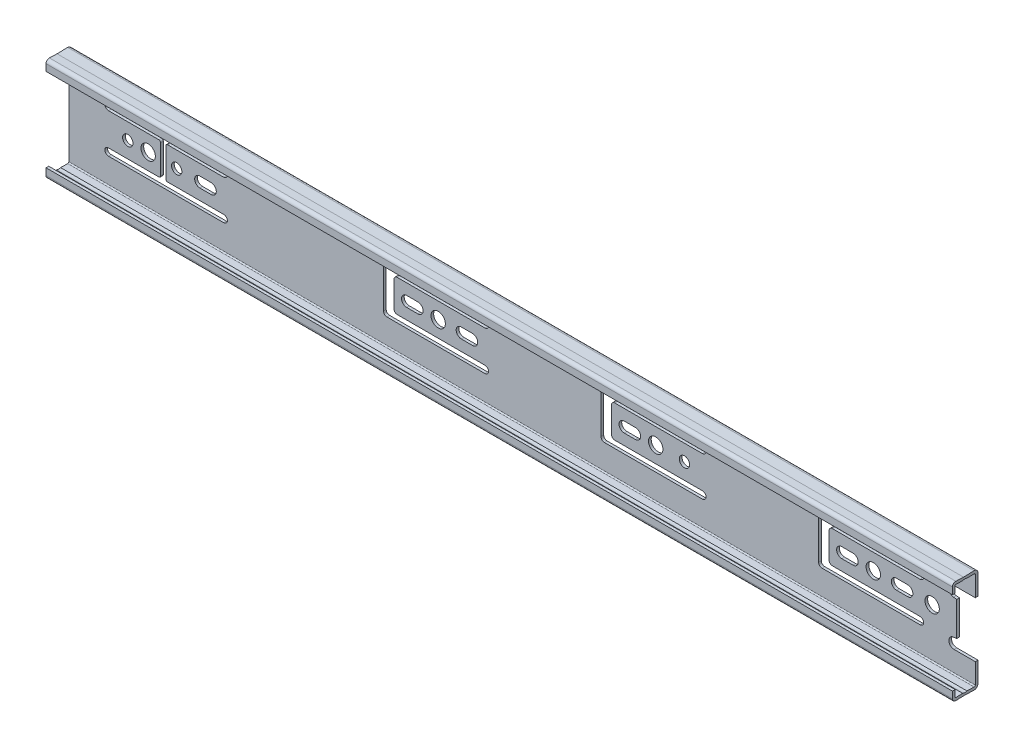
SolidWorks part; units mm, degrees
ref_plane "Front" through (0, 0, 0) normal (0, 0, 1) x (1, 0, 0)
ref_plane "Top" through (0, 0, 0) normal (0, 1, 0) x (1, 0, 0)
ref_plane "Right" through (0, 0, 0) normal (1, 0, 0) x (0, 0, -1)
sketch "Sketch1" plane through (0, 0, 0) normal (1, 0, 0) x (0, 0, -1)
  line L1 (5.6388, 0) -> (-5.6388, 0) construction
  line L4 (-4.1393, 22.8203) -> (-0.7433, 22.6989)
  line L5 (-1.1312, 21.5182) -> (-4.1819, 21.6273)
  line L6 (-4.445, 18.415) -> (-5.6388, 18.415)
  line L7 (-4.445, 21.3734) -> (-4.445, 18.415)
  line L8 (-5.6388, 18.415) -> (-5.6388, 21.3734)
  line L9 (3.9237, 21.6269) -> (0.7619, 21.5441)
  line L10 (5.6388, 0) -> (5.6388, 21.1191)
  line L11 (4.445, 21.1191) -> (4.445, 0)
  line L12 (5.6388, 0) -> (4.445, 0)
  line L13 (-0.7433, 22.6989) -> (3.8925, 22.8203)
  arc A0 (-4.445, 21.3734) -> (-4.1819, 21.6273) centre (-4.191, 21.3734) cw
  arc A1 (-5.6388, 21.3734) -> (-4.1393, 22.8203) centre (-4.191, 21.3734) cw
  arc A3 (3.9237, 21.6269) -> (4.445, 21.1191) centre (3.937, 21.1191) cw
  arc A4 (3.8925, 22.8203) -> (5.6388, 21.1191) centre (3.937, 21.1191) cw
  arc A5 (-1.1312, 21.5182) -> (0.7619, 21.5441) centre (-0.1524, 19.1744) cw
  dimension "D2" = 19.1744
  dimension "D7" = 0.254
  dimension "D8" = 0.508
  dimension "D6" = 2.54
  dimension "D9" = 1.1938
  dimension "D10" = 88.5
  dimension "D1" = 11.2776
  dimension "D3" = 5.7912
  dimension "D4" = 36.83
  dimension "D5" = 1.1938
  dimension "D11" = 87.953
  dimension "D12" = 45.6406
extrude "Extrude1" add sketch "Sketch1" along normal mid plane 400.05
ref_plane "Travel / 2" through (-403.225, 0, 0) normal (-1, 0, 0) x (0, 0, 1)
sketch "Sketch2" plane through (-403.225, 0, 0) normal (-1, 0, 0) x (0, 0, 1)
  line L0 (0.0254, 6.1159) -> (0.0254, 0)
  line L2 (-5.6388, 0) -> (5.6388, 0) construction
  line L3 (5.6388, 21.3734) -> (5.6388, 18.415) construction
  line L7 (-4.445, 21.1191) -> (-4.445, 0) construction
  line L8 (-5.6388, 0) -> (-5.6388, 21.1191) construction
  line L13 (-3.5306, 16.3766) -> (-3.5306, 9.5217)
  line L46 (-2.3867, 7.7262) -> (-0.4146, 6.8065)
  arc A0 (0.0254, 6.1159) -> (-0.4146, 6.8065) centre (-0.7366, 6.1159) ccw
  arc A1 (-1.5056, 17.2916) -> (1.2415, 16.9143) centre (0.1524, 19.1744) ccw
  arc A4 (1.1312, 21.5182) -> (-0.7619, 21.5441) centre (0.1524, 19.1744) ccw construction
  arc A19 (-3.5306, 9.5217) -> (-2.3867, 7.7262) centre (-1.5494, 9.5217) ccw
  arc A25 (-1.5056, 17.2916) -> (-3.5306, 16.3766) centre (-2.3114, 16.3766) ccw
  arc A51 (5.7404, 15.6277) -> (1.2415, 16.9143) centre (2.7686, 13.7451) ccw
  dimension "D2" = 8.4074
  dimension "D3" = 27.4903
  dimension "D6" = 1.9812
  dimension "D8" = 12.2319
  dimension "D10" = 2.5088
  dimension "D11" = 1.2192
  dimension "D4" = 0.762
  dimension "D5" = 4.4704
  dimension "D7" = 115
  dimension "D9" = 19.0435
  dimension "D13" = 11.3792
extrude "Middle Member" add sketch "Sketch2" against normal blind 400.05 separate body thin thin type one direction reverse wall 1.2192
ref_plane "Travel" through (-606.425, 0, 0) normal (-1, 0, 0) x (0, 0, 1)
sketch "Sketch3" plane through (-606.425, 0, 0) normal (-1, 0, 0) x (0, 0, 1)
  line L0 (1.2446, 0) -> (0.0254, 0) construction
  line L1 (-5.6388, 0) -> (-5.6388, 21.1191) construction
  line L56 (7.0612, 0) -> (7.0612, 10.6235)
  line L93 (5.5372, 12.1475) -> (5.1643, 12.1475)
  arc A0 (1.2082, 11.9072) -> (4.2365, 11.8325) centre (2.7686, 13.7451) ccw
  arc A29 (7.0612, 10.6235) -> (5.5372, 12.1475) centre (5.5372, 10.6235) ccw
  arc A53 (5.1643, 12.1475) -> (4.2365, 11.8325) centre (5.1643, 10.6235) ccw
  dimension "D1" = 1.524
  dimension "D4" = 1.524
  dimension "D5" = 2.411
  dimension "D2" = 12.7
  dimension "D3" = 12.1475
  dimension "D6" = 5.853
extrude "Drawer Member" add sketch "Sketch3" against normal blind 400.05 thin thin type one direction wall 1.397
sketch "Sketch6" plane through (0, 0, 7.0612) normal (0, 0, 1) x (1, 0, 0)
  line L1 (-606.425, 0) -> (-604.52, 0)
  line L2 (-606.425, 0) -> (-606.425, 12.1475)
  line L3 (-606.425, 12.1475) -> (-604.52, 12.1475)
  line L4 (-604.52, 0) -> (-604.52, 12.1475)
  line L5 (-206.375, 12.1475) -> (-606.425, 12.1475) construction
  line L7 (-606.425, 10.6235) -> (-606.425, 0) construction
  line L8 (-206.375, 0) -> (-606.425, 0) construction
  dimension "D1" = 1.905
extrude "Cut-Extrude1" cut sketch "Sketch6" against normal through all
sketch "Sketch8" plane through (0, 0, -4.445) normal (0, 0, 1) x (1, 0, 0)
  line L0 (190.3865, 7.6456) -> (191.8208, 7.493)
  line L1 (200.025, 12.2048) -> (190.6284, 12.2048)
  line L2 (191.8208, 7.493) -> (191.8208, 0)
  line L3 (200.025, 0) -> (-200.025, 0) construction
  line L4 (200.025, 21.1191) -> (200.025, 0) construction
  line L5 (200.025, 12.2048) -> (200.025, 0)
  line L6 (200.025, 0) -> (191.8208, 0)
  arc A0 (190.6284, 12.2048) -> (190.3865, 7.6456) centre (190.6284, 9.9188) ccw
  dimension "D3" = 9.9188
  dimension "D1" = 12.2048
  dimension "D2" = 8.2042
  dimension "D4" = 9.3966
  dimension "D5" = 7.493
extrude "Cut-Extrude2" cut sketch "Sketch8" against normal up to next (1.1938 mm away)
sketch "Sketch11" plane through (0, 0, 7.0612) normal (0, 0, 1) x (1, 0, 0)
  line L0 (-212.09, 5.9678) -> (-212.09, 0)
  line L8 (-206.375, 8.5893) -> (-212.2343, 7.2212)
  line L11 (-212.09, 0) -> (-206.375, 0)
  line L12 (-206.375, 0) -> (-206.375, 8.5893)
  arc A1 (-212.2343, 7.2212) -> (-212.09, 5.9678) centre (-212.0899, 6.6028) ccw
  dimension "D3" = 0.635
  dimension "D1" = 5.715
  dimension "D2" = 8.5893
  dimension "D4" = 5.9678
  dimension "D5" = 103.143
extrude "Cut-Extrude3" cut sketch "Sketch11" against normal up to next (1.397 mm away)
sketch "Sketch12" plane through (0, 0, 1.2446) normal (0, 0, 1) x (1, 0, 0)
  line L0 (-3.175, 12.065) -> (-13.335, 12.065)
  line L1 (-3.175, 16.3766) -> (-3.175, 9.5217) construction
  line L2 (-15.875, 9.525) -> (-15.875, 0)
  line L3 (-3.175, 0) -> (-403.225, 0) construction
  line L4 (-15.875, 0) -> (-3.175, 0)
  line L5 (-3.175, 0) -> (-3.175, 12.065)
  arc A0 (-13.335, 12.065) -> (-15.875, 9.525) centre (-13.335, 9.525) ccw
  point P11 (-15.875, 12.065)
  dimension "D3" = 2.54
  dimension "D1" = 12.7
  dimension "D2" = 12.065
extrude "Cut-Extrude4" cut sketch "Sketch12" against normal through all
sketch "Sketch13" plane through (0, 0, -4.445) normal (0, 0, 1) x (1, 0, 0)
  line L0 (-131.6367, 7.112) -> (-156.4652, 7.112)
  line L1 (191.8208, 0) -> (-200.025, 0) construction
  line L2 (-139.7266, 0) -> (-139.7266, 4.2392) construction
  line L3 (-182.5637, 10.287) -> (-131.6367, 10.287)
  line L4 (-200.025, 21.1191) -> (-200.025, 0) construction
  line L5 (-160.2752, 7.112) -> (-182.5637, 7.112)
  line L6 (-159.5132, 0) -> (-159.5132, 6.35)
  line L7 (-157.2272, 6.35) -> (-157.2272, 0)
  line L8 (-137.2501, 2.286) -> (-142.2031, 2.286)
  line L13 (-176.3026, 0) -> (-171.7306, 0)
  line L14 (-168.2, 0) -> (-161.85, 0)
  line L15 (-159.5132, 0) -> (-157.2272, 0)
  line L16 (-154.7126, 0) -> (-150.1406, 0)
  line L17 (-144.4891, 0) -> (-134.9641, 0)
  arc A1 (-182.5637, 10.287) -> (-182.5637, 7.112) centre (-182.5637, 8.6995) ccw
  arc A2 (-159.5132, 6.35) -> (-160.2752, 7.112) centre (-160.2752, 6.35) ccw
  arc A4 (-156.4652, 7.112) -> (-157.2272, 6.35) centre (-156.4652, 6.35) ccw
  arc A7 (-131.6367, 7.112) -> (-131.6367, 10.287) centre (-131.6367, 8.6995) ccw
  arc A8 (-161.85, 0) -> (-168.2, 0) centre (-165.025, 0) ccw
  arc A9 (-171.7306, 0) -> (-176.3026, 0) centre (-174.0166, 0) ccw
  arc A10 (-150.1406, 0) -> (-154.7126, 0) centre (-152.4266, 0) ccw
  arc A11 (-134.9641, 0) -> (-137.2501, 2.286) centre (-137.2501, 0) ccw
  arc A12 (-142.2031, 2.286) -> (-144.4891, 0) centre (-142.2031, 0) ccw
  dimension "D3" = 2.286
  dimension "D4" = 3.175
  dimension "D7" = 8.9916
  dimension "D8" = 21.59
  dimension "D9" = 34.29
  dimension "D10" = 0.762
  dimension "D11" = 17.5387
  dimension "D12" = 9.525
  dimension "D13" = 5.5118
  dimension "D14" = 35
  dimension "D1" = 3.175
  dimension "D2" = 50.927
  dimension "D5" = 2.286
  dimension "D6" = 10.287
extrude "Cut-Extrude5" cut sketch "Sketch13" against normal up to next (1.1938 mm away)
sketch "Sketch32" plane through (0, 0, -5.6388) normal (0, 0, -1) x (-1, 0, 0)
  line L0 (19.5625, 0) -> (29.0875, 0)
  line L1 (33.85, 0) -> (40.2, 0)
  line L2 (43.6925, 0) -> (53.2175, 0)
  line L3 (56.583, 0) -> (61.155, 0)
  line L4 (-191.8208, 0) -> (134.9641, 0) construction
  line L5 (182.5637, 10.287) -> (131.6367, 10.287) construction
  line L6 (131.6367, 7.112) -> (156.4652, 7.112) construction
  line L7 (48.455, 2.286) -> (48.455, -3.4269) construction
  line L8 (24.325, 2.286) -> (24.325, -3.4269) construction
  line L14 (16.3875, 10.287) -> (59.631, 10.287)
  line L15 (55.059, 7.112) -> (16.3875, 7.112)
  line L17 (61.155, 8.763) -> (61.155, 0)
  line L18 (56.583, 0) -> (56.583, 5.588)
  line L23 (21.8485, 2.286) -> (26.8015, 2.286)
  line L25 (45.9785, 2.286) -> (50.9315, 2.286)
  arc A0 (168.2, 0) -> (161.85, 0) centre (165.025, 0) ccw construction
  arc A13 (61.155, 8.763) -> (59.631, 10.287) centre (59.631, 8.763) ccw
  arc A14 (56.583, 5.588) -> (55.059, 7.112) centre (55.059, 5.588) ccw
  arc A17 (16.3875, 10.287) -> (16.3875, 7.112) centre (16.3875, 8.6995) ccw
  arc A20 (29.0875, 0) -> (26.8015, 2.286) centre (26.8015, 0) ccw
  arc A21 (21.8485, 2.286) -> (19.5625, 0) centre (21.8485, 0) ccw
  arc A22 (40.2, 0) -> (33.85, 0) centre (37.025, 0) ccw
  arc A24 (53.2175, 0) -> (50.9315, 2.286) centre (50.9315, 0) ccw
  arc A25 (45.9785, 2.286) -> (43.6925, 0) centre (45.9785, 0) ccw
  dimension "D2" = 1.524
  dimension "D3" = 3.175
  dimension "D4" = 9.525
  dimension "D5" = 2.286
  dimension "D6" = 11.43
  dimension "D7" = 12.7
  dimension "D8" = 24.13
  dimension "D9" = 20.6375
  dimension "D10" = 128
  dimension "D1" = 4.572
extrude "Cut-Extrude14" cut sketch "Sketch32" against normal up to next (1.1938 mm away)
sketch "Sketch33" plane through (83.6094, 0.8125, -5.6388) normal (0, 0, -1) x (-1, 0, 0)
  line L0 (7.1719, -0.8125) -> (16.6969, -0.8125) construction
  line L1 (21.4594, -0.8125) -> (27.8094, -0.8125)
  line L2 (31.3019, -0.8125) -> (40.8269, -0.8125)
  line L3 (44.1924, -0.8125) -> (48.7644, -0.8125)
  line L4 (9.6484, -0.8125) -> (14.2204, -0.8125)
  line L7 (36.0644, 1.4735) -> (36.0644, -4.2394) construction
  line L8 (11.9344, 1.4735) -> (11.9344, -3.4269) construction
  line L9 (-108.2114, -0.8125) -> (103.1719, -0.8125) construction
  line L10 (143.2404, 9.4745) -> (99.9969, 9.4745) construction
  line L11 (99.9969, 6.2995) -> (138.6684, 6.2995) construction
  line L14 (3.9969, 9.4745) -> (47.2404, 9.4745)
  line L15 (42.6684, 6.2995) -> (3.9969, 6.2995)
  line L17 (48.7644, 7.9505) -> (48.7644, -0.8125)
  line L18 (44.1924, -0.8125) -> (44.1924, 4.7755)
  line L23 (9.4579, 1.4735) -> (14.4109, 1.4735) construction
  line L25 (33.5879, 1.4735) -> (38.5409, 1.4735)
  arc A0 (14.2204, -0.8125) -> (9.6484, -0.8125) centre (11.9344, -0.8125) ccw
  arc A1 (251.8094, -0.8125) -> (245.4594, -0.8125) centre (248.6344, -0.8125) ccw construction
  arc A13 (48.7644, 7.9505) -> (47.2404, 9.4745) centre (47.2404, 7.9505) ccw
  arc A14 (44.1924, 4.7755) -> (42.6684, 6.2995) centre (42.6684, 4.7755) ccw
  arc A17 (3.9969, 9.4745) -> (3.9969, 6.2995) centre (3.9969, 7.887) ccw
  arc A20 (16.6969, -0.8125) -> (14.4109, 1.4735) centre (14.4109, -0.8125) ccw construction
  arc A21 (9.4579, 1.4735) -> (7.1719, -0.8125) centre (9.4579, -0.8125) ccw construction
  arc A22 (27.8094, -0.8125) -> (21.4594, -0.8125) centre (24.6344, -0.8125) ccw
  arc A24 (40.8269, -0.8125) -> (38.5409, 1.4735) centre (38.5409, -0.8125) ccw
  arc A25 (33.5879, 1.4735) -> (31.3019, -0.8125) centre (33.5879, -0.8125) ccw
  dimension "D2" = 1.524
  dimension "D3" = 3.175
  dimension "D4" = 9.525
  dimension "D5" = 2.286
  dimension "D6" = 11.43
  dimension "D7" = 12.7
  dimension "D8" = 24.13
  dimension "D9" = 20.6375
  dimension "D10" = 224
  dimension "D1" = 4.572
extrude "Cut F" cut sketch "Sketch33" against normal up to next (1.1938 mm away)
sketch "Sketch34" plane through (169.8236, 1.4527, -5.6388) normal (0, 0, -1) x (-1, 0, 0)
  line L0 (-2.6539, -1.4527) -> (6.8711, -1.4527)
  line L1 (11.6336, -1.4527) -> (17.9836, -1.4527)
  line L2 (21.4761, -1.4527) -> (31.0011, -1.4527)
  line L3 (34.3666, -1.4527) -> (38.9386, -1.4527)
  line L4 (-21.9972, -1.4527) -> (95.8626, -1.4527) construction
  line L7 (26.2386, 0.8333) -> (26.2386, -4.8796) construction
  line L8 (2.1086, 0.8333) -> (2.1086, -4.0671) construction
  line L9 (229.4546, 8.8343) -> (186.2111, 8.8343) construction
  line L10 (186.2111, 5.6593) -> (224.8826, 5.6593) construction
  line L14 (-5.8289, 8.8343) -> (37.4146, 8.8343)
  line L15 (32.8426, 5.6593) -> (-5.8289, 5.6593)
  line L17 (38.9386, 7.3103) -> (38.9386, -1.4527)
  line L18 (34.3666, -1.4527) -> (34.3666, 4.1353)
  line L23 (-0.3679, 0.8333) -> (4.5851, 0.8333)
  line L25 (23.7621, 0.8333) -> (28.7151, 0.8333)
  arc A0 (338.0236, -1.4527) -> (331.6736, -1.4527) centre (334.8486, -1.4527) ccw construction
  arc A13 (38.9386, 7.3103) -> (37.4146, 8.8343) centre (37.4146, 7.3103) ccw
  arc A14 (34.3666, 4.1353) -> (32.8426, 5.6593) centre (32.8426, 4.1353) ccw
  arc A17 (-5.8289, 8.8343) -> (-5.8289, 5.6593) centre (-5.8289, 7.2468) ccw
  arc A20 (6.8711, -1.4527) -> (4.5851, 0.8333) centre (4.5851, -1.4527) ccw
  arc A21 (-0.3679, 0.8333) -> (-2.6539, -1.4527) centre (-0.3679, -1.4527) ccw
  arc A22 (17.9836, -1.4527) -> (11.6336, -1.4527) centre (14.8086, -1.4527) ccw
  arc A24 (31.0011, -1.4527) -> (28.7151, 0.8333) centre (28.7151, -1.4527) ccw
  arc A25 (23.7621, 0.8333) -> (21.4761, -1.4527) centre (23.7621, -1.4527) ccw
  dimension "D2" = 1.524
  dimension "D3" = 3.175
  dimension "D4" = 9.525
  dimension "D5" = 2.286
  dimension "D6" = 11.43
  dimension "D7" = 12.7
  dimension "D8" = 24.13
  dimension "D9" = 20.6375
  dimension "D10" = 320.04
  dimension "D1" = 4.572
extrude "Cut G" cut sketch "Sketch34" against normal up to next (1.1938 mm away)
sketch "Sketch31" plane through (0, 0, -5.6388) normal (0, 0, -1) x (-1, 0, 0)
  line L0 (-200.025, 12.2048) -> (-200.025, 21.1191) construction
  line L1 (-191.8208, 0) -> (-172.4775, 0) construction
  line L2 (-184.15, 0) -> (-177.8, 0)
  arc A0 (-177.8, 0) -> (-184.15, 0) centre (-180.975, 0) ccw
  dimension "D1" = 19.05
  dimension "D2" = 6.35
extrude "Cut-Extrude15" cut sketch "Sketch31" against normal up to next (1.1938 mm away)
sketch "Sketch26" plane through (0, 0, 1.2446) normal (0, 0, 1) x (1, 0, 0)
  line L0 (-176.3026, 0) -> (-134.9641, 0)
  line L1 (-171.4766, 4.826) -> (-139.7901, 4.826)
  line L2 (-19.5625, 0) -> (-53.2175, 0)
  line L3 (-48.3915, 4.826) -> (-24.3885, 4.826)
  line L4 (76.4375, 0) -> (42.7825, 0)
  line L5 (47.6085, 4.826) -> (71.6115, 4.826)
  arc A0 (-176.3026, 0) -> (-171.4766, 4.826) centre (-171.4766, 0) cw
  arc A1 (-134.9641, 0) -> (-139.7901, 4.826) centre (-139.7901, 0) ccw
  arc A2 (-53.2175, 0) -> (-48.3915, 4.826) centre (-48.3915, 0) cw
  arc A3 (-24.3885, 4.826) -> (-19.5625, 0) centre (-24.3885, 0) cw
  arc A4 (-19.5625, 0) -> (-21.8485, 2.286) centre (-21.8485, 0) ccw construction
  arc A5 (-50.9315, 2.286) -> (-53.2175, 0) centre (-50.9315, 0) ccw construction
  arc A6 (42.7825, 0) -> (47.6085, 4.826) centre (47.6085, 0) cw
  arc A7 (71.6115, 4.826) -> (76.4375, 0) centre (71.6115, 0) cw
  dimension "D1" = 4.826
extrude "Cut-Extrude17" cut sketch "Sketch26" against normal up to next (1.2192 mm away)
ref_plane "Plane3" through (-187.325, 0, 0) normal (-1, 0, 0) x (0, 0, 1)
sketch "Sketch27" plane through (-187.325, 0, 0) normal (-1, 0, 0) x (0, 0, 1)
  line L0 (0.1524, 21.6832) -> (0.1524, 16.6656)
  line L1 (0.1524, 23.635) -> (0.1524, 15.2838) construction
  arc A0 (0.1524, 16.6656) -> (0.1524, 21.6832) centre (0.1524, 19.1744) ccw
  arc A1 (-1.5056, 17.2916) -> (1.2415, 16.9143) centre (0.1524, 19.1744) ccw construction
revolve "Revolve1" add sketch "Sketch27" angle 360 about L1
pattern_linear "LPattern1" count 6 spacing 19.05 along (1, 0, 0) of bodies 128
sketch "Sketch28" plane through (-187.325, 0, 0) normal (-1, 0, 0) x (0, 0, 1)
  line L0 (2.6612, 19.1744) -> (-2.3564, 19.1744) construction
  line L1 (3.9624, 18.7934) -> (-3.6576, 18.7934)
  line L2 (3.9624, 18.7934) -> (3.9624, 19.5554)
  line L3 (3.9624, 19.5554) -> (-3.6576, 19.5554)
  line L4 (-3.6576, 18.7934) -> (-3.6576, 19.5554)
  line L5 (0.1524, 20.5465) -> (0.1524, 17.804) construction
  circle A1 centre (0.1524, 19.1744) radius 2.5088 construction
  point P8 (0.1524, 19.1744)
  dimension "D1" = 7.62
  dimension "D2" = 0.762
extrude "Extrude7" add sketch "Sketch28" along normal blind 6.35 and the other way blind 101.6
ref_plane "Plane4" through (-365.125, 0, 0) normal (-1, 0, 0) x (0, 0, 1)
sketch "Sketch29" plane through (-365.125, 0, 0) normal (-1, 0, 0) x (0, 0, 1)
  line L0 (2.7686, 16.0438) -> (2.7686, 11.4464)
  line L1 (2.7686, 16.6801) -> (2.7686, 10.2973) construction
  arc A0 (2.7686, 11.4464) -> (2.7686, 16.0438) centre (2.7686, 13.7451) ccw
  arc A1 (4.7105, 14.9753) -> (1.7707, 15.816) centre (2.7686, 13.7451) ccw construction
revolve "Revolve2" add sketch "Sketch29" angle 360 about L1
pattern_linear "LPattern2" count 6 spacing 19.05 along (1, 0, 0) of bodies 135
sketch "Sketch30" plane through (-365.125, 0, 0) normal (-1, 0, 0) x (0, 0, 1)
  line L0 (0.4699, 13.7451) -> (5.0673, 13.7451) construction
  line L1 (3.9624, 18.7934) -> (3.9624, 19.5554) construction
  line L2 (0.2286, 14.1261) -> (5.3086, 14.1261)
  line L3 (0.2286, 14.1261) -> (0.2286, 13.3641)
  line L4 (0.2286, 13.3641) -> (5.3086, 13.3641)
  line L5 (5.3086, 14.1261) -> (5.3086, 13.3641)
  line L7 (2.7686, 14.2437) -> (2.7686, 12.7853) construction
  circle A0 centre (2.7686, 13.7451) radius 2.2987 construction
  point P4 (2.7686, 13.7451)
  dimension "D1" = 5.08
extrude "Extrude8" add sketch "Sketch30" along normal blind 6.35 and the other way blind 101.6
mirror "Mirror3" about plane through (0, 0, 0) normal (0, 1, 0) of bodies 118 163 159 117 124 126 127 119
mirror "Mirror5" about plane through (0, 0, 0) normal (0, 1, 0) of bodies 141 134
delete or keep bodies "Sólido-Eliminar/Conservar 1" type delete bodies bodies 161
delete or keep bodies "Sólido-Eliminar/Conservar 2" type delete bodies bodies 150
delete or keep bodies "Sólido-Eliminar/Conservar 3" type delete bodies bodies 134 141 152 153
